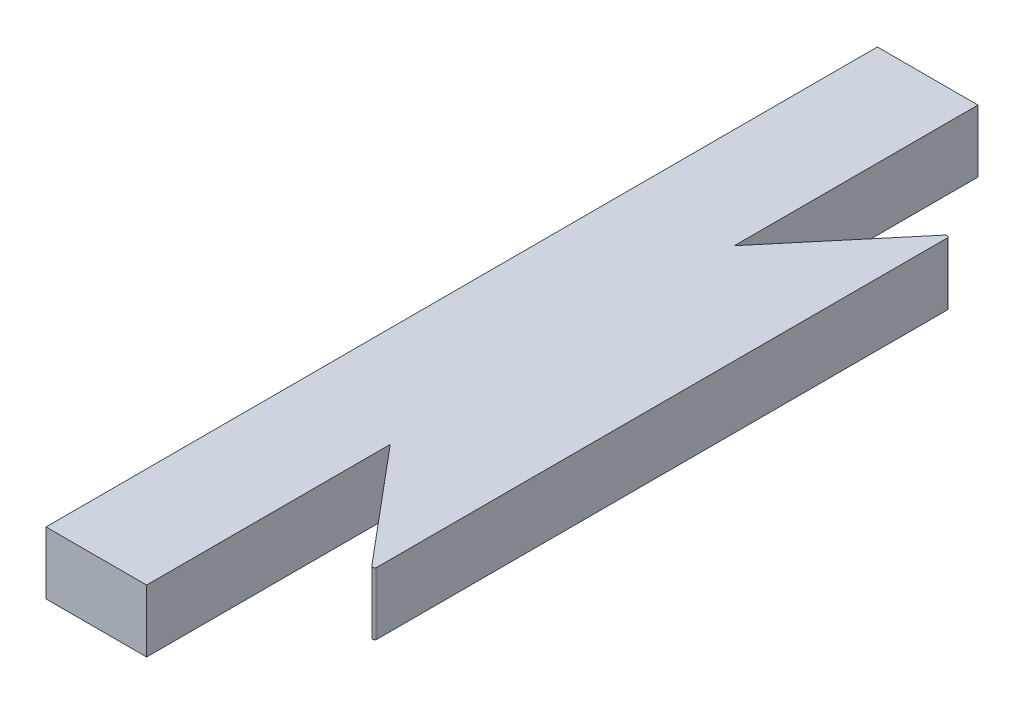
SolidWorks part; units mm, degrees
ref_plane "Alzado" through (0, 0, 0) normal (0, 0, 1) x (1, 0, 0)
ref_plane "Planta" through (0, 0, 0) normal (0, 1, 0) x (1, 0, 0)
ref_plane "Vista lateral" through (0, 0, 0) normal (1, 0, 0) x (0, 0, -1)
sketch "Croquis1" plane through (0, 0, 0) normal (0, 1, 0) x (1, 0, 0)
  line L0 (65, 8.2796) -> (69.8, 14)
  line L1 (-65, -20) -> (65, -20)
  line L2 (-65, -20) -> (-65, 20)
  line L3 (-65, 20) -> (65, 20)
  line L4 (65, -20) -> (65, -8.2796)
  line L5 (-65, -20) -> (65, 20) construction
  line L6 (-65, 20) -> (65, -20) construction
  line L7 (69.8, 14) -> (69.8, -14)
  line L8 (69.8, -14) -> (65, -8.2796)
  line L9 (65, 8.2796) -> (65, 20)
  line L10 (0, 0) -> (77.1384, 0) construction
  line L12 (10, 9.5) -> (40, 9.5)
  line L13 (10, 9.5) -> (10, 12.5)
  line L14 (10, 12.5) -> (40, 12.5)
  line L15 (40, 9.5) -> (40, 12.5)
  line L16 (10, 9.5) -> (40, 12.5) construction
  line L17 (10, 12.5) -> (40, 9.5) construction
  line L18 (10, -12.5) -> (40, -12.5)
  line L19 (10, -12.5) -> (10, -9.5)
  line L20 (10, -9.5) -> (40, -9.5)
  line L21 (40, -12.5) -> (40, -9.5)
  line L22 (10, -12.5) -> (40, -9.5) construction
  line L23 (10, -9.5) -> (40, -12.5) construction
  circle A2 centre (-50.1299, 0) radius 11
  circle A3 centre (-50.1299, 0) radius 12.5 construction
  circle A4 centre (-28.5951, 0) radius 2
  circle A5 centre (-13.5951, 0) radius 2
  circle A6 centre (50, 0) radius 2
  point P0 (0, 0)
  point P8 (69.8, 0)
  point P19 (25, 11)
  point P35 (25, -11)
  dimension "D8" = 22
  dimension "D12" = 25
  dimension "D13" = 4
  dimension "D14" = 4
  dimension "D17" = 4
  dimension "D1" = 130
  dimension "D2" = 4.8
  dimension "D3" = 40
  dimension "D5" = 28
  dimension "D6" = 40
  dimension "D9" = 3
  dimension "D10" = 30
  dimension "D11" = 40
  dimension "D15" = 15
  dimension "D16" = 10
  dimension "D18" = 12.5
  dimension "D19" = 12.5
extrude "Saliente-Extruir1" add sketch "Croquis1" along normal blind 3
sketch "Croquis2" plane through (0, 3, 0) normal (0, 1, 0) x (1, 0, 0)
  circle A0 centre (-50.1299, 0) radius 11
  circle A1 centre (-50.1299, 0) radius 13
  dimension "D1" = 2
extrude "Saliente-Extruir2" add sketch "Croquis2" along normal blind 4
sketch "Croquis3" plane through (0, 7, 0) normal (0, 1, 0) x (1, 0, 0)
  circle A0 centre (-50.1299, 0) radius 13
  circle A1 centre (-50.1299, 0) radius 9
  dimension "D1" = 18
extrude "Saliente-Extruir3" add sketch "Croquis3" along normal blind 2
chamfer "Chaflán1" distance 2 angle 45 1 edges at (-50.1299, 9, 13)
chamfer "Chaflán2" distance 10 angle 45 2 edges at (-65, 1.5, 20) (-65, 1.5, -20)
sketch "Croquis4" plane through (0, 3, 0) normal (0, 1, 0) x (1, 0, 0)
  line L1 (60.1587, 28.398) -> (-68.6747, 28.398)
  line L2 (60.1587, 28.398) -> (60.1587, -29.8358)
  line L3 (60.1587, -29.8358) -> (-68.6747, -29.8358)
  line L4 (-68.6747, 28.398) -> (-68.6747, -29.8358)
extrude "Cortar-Extruir1" cut sketch "Croquis4" against normal blind 10 and the other way blind 10
fillet "Redondeo1" radius 0.1 2 edges at (69.8, 1.5, -14) (69.8, 1.5, 14)
